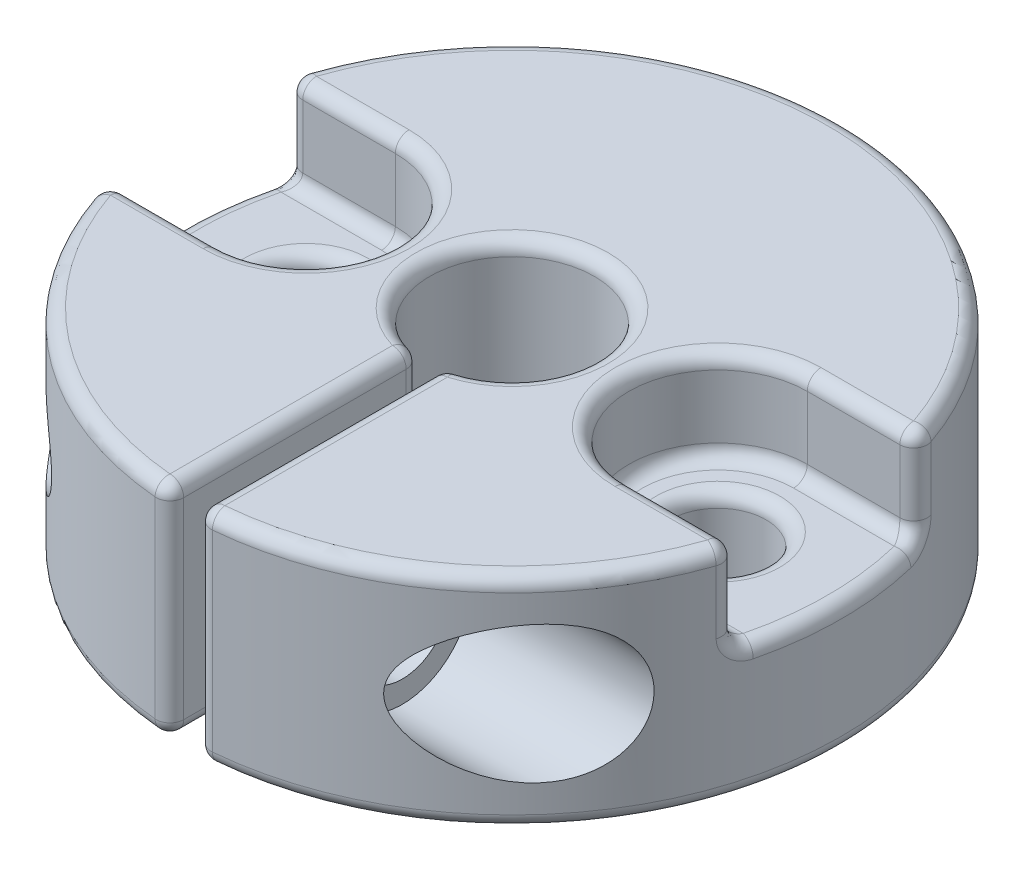
SolidWorks part; units mm, degrees
ref_plane "Front Plane" through (0, 0, 0) normal (0, 0, 1) x (1, 0, 0)
ref_plane "Top Plane" through (0, 0, 0) normal (0, 1, 0) x (1, 0, 0)
ref_plane "Right Plane" through (0, 0, 0) normal (1, 0, 0) x (0, 0, -1)
sketch "Sketch1" plane through (0, 0, 0) normal (0, 1, 0) x (1, 0, 0)
  line L0 (0, 0) -> (-12, 0) construction
  line L1 (0, -12) -> (0, 12) construction
  line L2 (-0.5, -12) -> (-0.5, -2.958)
  line L3 (0.5, -12) -> (-0.5, -12)
  line L4 (0.5, -12) -> (0.5, -2.958)
  circle A0 centre (0, 0) radius 12
  circle A1 centre (-7.5, 0) radius 1.75
  circle A2 centre (7.5, 0) radius 1.75
  circle A3 centre (0, 0) radius 3 construction
  arc A4 (-0.5, -2.958) -> (0.5, -2.958) centre (0, 0) cw
  dimension "D1" = 24
  dimension "D2" = 3.5
  dimension "D4" = 6
  dimension "D3" = 15
  dimension "D5" = 1
extrude "Boss-Extrude1" add sketch "Sketch1" along normal blind 8 contours L2 A4 L4 A0 A1 A2 region at (-8.0717, 0, -8.4154)
sketch "Sketch2" plane through (0, 8, 0) normal (0, 1, 0) x (1, 0, 0)
  line L0 (-7.5, 3.25) -> (-11.5515, 3.25)
  line L1 (-7.5, -3.25) -> (-11.5515, -3.25)
  line L2 (0, 0) -> (0, 12) construction
  line L3 (7.5, -3.25) -> (11.5515, -3.25)
  line L4 (7.5, 3.25) -> (11.5515, 3.25)
  circle A0 centre (-7.5, 0) radius 3.25 construction
  arc A1 (0.5, -11.9896) -> (-0.5, -11.9896) centre (0, 0) ccw construction
  arc A2 (-7.5, 3.25) -> (-7.5, -3.25) centre (-7.5, 0) cw
  arc A3 (-11.5515, -3.25) -> (-11.5515, 3.25) centre (0, 0) cw
  arc A4 (7.5, 3.25) -> (7.5, -3.25) centre (7.5, 0) ccw
  arc A5 (11.5515, -3.25) -> (11.5515, 3.25) centre (0, 0) ccw
  dimension "D1" = 6.5
extrude "Cut-Extrude1" cut sketch "Sketch2" against normal blind 3.3
ref_plane "Plane1" through (12, 0, 0) normal (1, 0, 0) x (0, 0, -1)
sketch "Sketch3" plane through (12, 0, 0) normal (1, 0, 0) x (0, 0, -1)
  line L0 (-11.9896, 4) -> (12, 4) construction
  line L1 (-11.9896, 8) -> (-11.9896, 0) construction
  line L2 (12, 0) -> (12, 8) construction
  circle A0 centre (-7.9948, 4) radius 2.5
  point P8 (0.0052, 4)
  dimension "D1" = 5
  dimension "D2" = 8
extrude "Cut-Extrude2" cut sketch "Sketch3" against normal blind 8
sketch "Sketch4" plane through (4, 0, 0) normal (1, 0, 0) x (0, 0, -1)
  circle A0 centre (-7.9948, 4) radius 1.7
  dimension "D1" = 3.4
extrude "Cut-Extrude3" cut sketch "Sketch4" against normal through all
fillet "Fillet1" radius 0.5 38 edges at (11.5515, 6.35, -3.25) (11.5515, 6.35, 3.25) (-11.5515, 6.35, 3.25) (-11.5515, 6.35, -3.25) (0.5, 4, 2.958) (0.5, 4, 11.9896) (0.5, 4, 9.6948) (-0.5, 4, 11.9896) (-0.5, 4, 2.958) (-0.5, 4, 9.6948) (7.5, 4.7, 1.75) (9.5258, 4.7, -3.25) (12, 4.7, 0) (9.5258, 4.7, 3.25) (4.25, 4.7, 0) (-9.5258, 4.7, 3.25) (-12, 4.7, 0) (-9.5258, 4.7, -3.25) (-4.25, 4.7, 0) (-7.5, 4.7, -1.75) (0, 0, -3) (0.5, 0, 7.4738) (0, 0, -12) (-0.5, 0, 7.4738) (7.5, 0, 1.75) (-7.5, 0, 1.75) (-4.25, 8, 0) (-9.5258, 8, -3.25) (0, 8, -12) (9.5258, 8, -3.25) (4.25, 8, 0) (9.5258, 8, 3.25) (7.4434, 8, 9.4125) (0.5, 8, 7.4738) (0, 8, -3) (-0.5, 8, 7.4738) (-7.4434, 8, 9.4125) (-9.5258, 8, 3.25)
